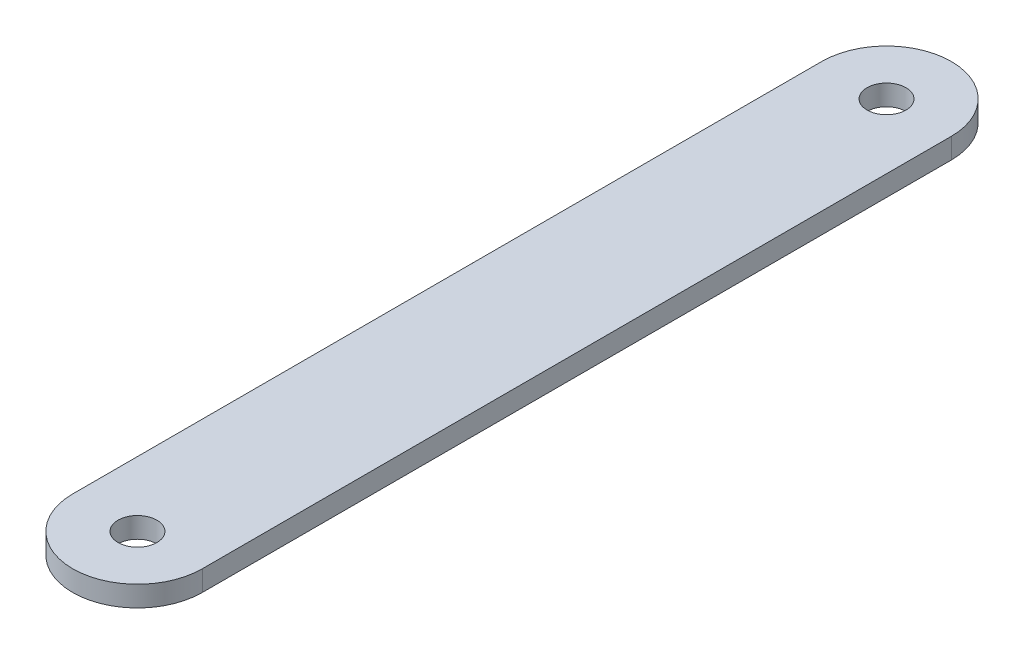
SolidWorks part; units mm, degrees
ref_plane "Front Plane" through (0, 0, 0) normal (0, 0, 1) x (1, 0, 0)
ref_plane "Top Plane" through (0, 0, 0) normal (0, 1, 0) x (1, 0, 0)
ref_plane "Right Plane" through (0, 0, 0) normal (1, 0, 0) x (0, 0, -1)
sketch "Sketch2" plane through (0, 0, 0) normal (0, 1, 0) x (1, 0, 0)
  line L0 (-5, 57.8) -> (-5, 0)
  line L1 (5, 57.8) -> (5, 0)
  circle A0 centre (0, 0) radius 1.5
  circle A1 centre (0, 57.8) radius 1.5
  arc A2 (5, 0) -> (-5, 0) centre (0, 0) cw
  arc A3 (5, 57.8) -> (-5, 57.8) centre (0, 57.8) ccw
  dimension "D2" = 3
  dimension "D3" = 5
  dimension "D1" = 57.8
extrude "Boss-Extrude1" add sketch "Sketch2" along normal blind 1.5875
